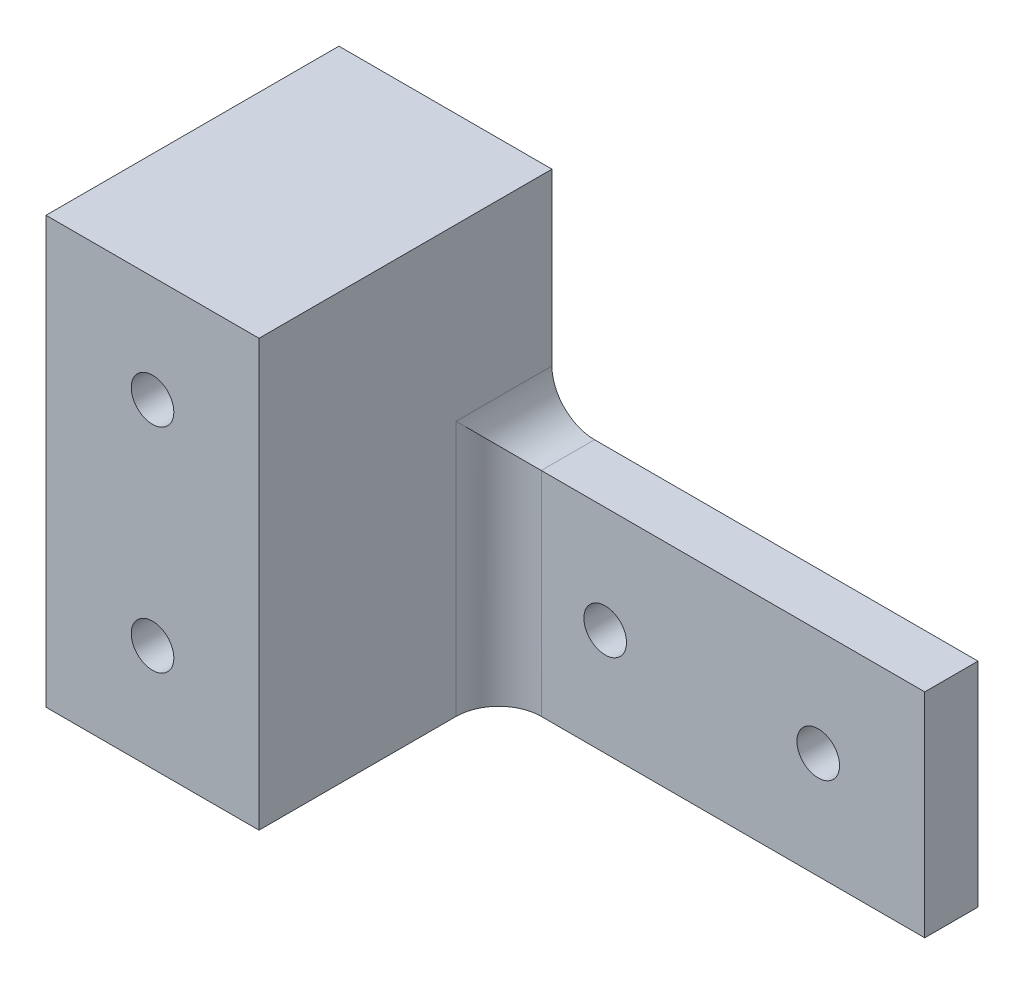
SolidWorks part; units mm, degrees
ref_plane "Front Plane" through (0, 0, 0) normal (0, 0, 1) x (1, 0, 0)
ref_plane "Top Plane" through (0, 0, 0) normal (0, 1, 0) x (1, 0, 0)
ref_plane "Right Plane" through (0, 0, 0) normal (1, 0, 0) x (0, 0, -1)
sketch "Sketch1" plane through (0, 0, 0) normal (0, 0, 1) x (1, 0, 0)
  line L0 (0, 0) -> (0, 50.8)
  line L1 (0, 50.8) -> (25.4, 50.8)
  line L2 (25.4, 50.8) -> (25.4, 25.4)
  line L3 (25.4, 25.4) -> (76.2, 25.4)
  line L4 (76.2, 25.4) -> (76.2, 0)
  line L5 (76.2, 0) -> (0, 0)
  dimension "D1" = 50.8
  dimension "D2" = 25.4
  dimension "3" = 76.2
extrude "Boss-Extrude1" add sketch "Sketch1" along normal blind 34.925
sketch "Sketch2" plane through (0, 0, 34.925) normal (0, 0, 1) x (1, 0, 0)
  line L0 (25.4, 50.8) -> (0, 50.8) construction
  line L1 (25.4, 25.4) -> (25.4, 50.8) construction
  line L2 (0, 0) -> (76.2, 0) construction
  circle A0 centre (12.7, 38.1) radius 2.54
  circle A1 centre (12.7, 12.7) radius 2.54
  circle A2 centre (38.1, 12.7) radius 2.54
  circle A3 centre (63.5, 12.7) radius 2.54
  dimension "D1" = 5.08
  dimension "D2" = 12.7
  dimension "D3" = 12.7
  dimension "D4" = 12.7
  dimension "D5" = 3
extrude "Cut-Extrude1" cut sketch "Sketch2" against normal through all
sketch "Sketch3" plane through (0, 0, 34.925) normal (0, 0, 1) x (1, 0, 0)
  line L0 (25.4, 50.8) -> (0, 50.8) construction
  line L1 (0, 0) -> (4.7625, 0)
  line L2 (0, 0) -> (0, 50.8)
  line L3 (0, 50.8) -> (4.7625, 50.8)
  line L4 (4.7625, 0) -> (4.7625, 50.8)
  dimension "D1" = 4.7625
sketch "Sketch4" plane through (0, 0, 0) normal (0, -1, 0) x (1, 0, 0)
  line L5 (76.2, 34.925) -> (25.4, 34.925)
  line L6 (76.2, 34.925) -> (76.2, 6.35)
  line L7 (76.2, 6.35) -> (25.4, 6.35)
  line L8 (25.4, 34.925) -> (25.4, 6.35)
  dimension "D1" = 28.575
  dimension "D2" = 50.8
extrude "Cut-Extrude3" cut sketch "Sketch4" against normal through all
fillet "Fillet1" radius 5.08 2 edges at (25.4, 25.4, 3.175) (25.4, 12.7, 6.35)
sketch "Sketch5" plane through (0, 0, 0) normal (0, 0, -1) x (-1, 0, 0)
  circle A0 centre (-12.7, 38.1) radius 4.064
  dimension "D1" = 8.128
extrude "Cut-Extrude4" cut sketch "Sketch5" against normal blind 7.62
